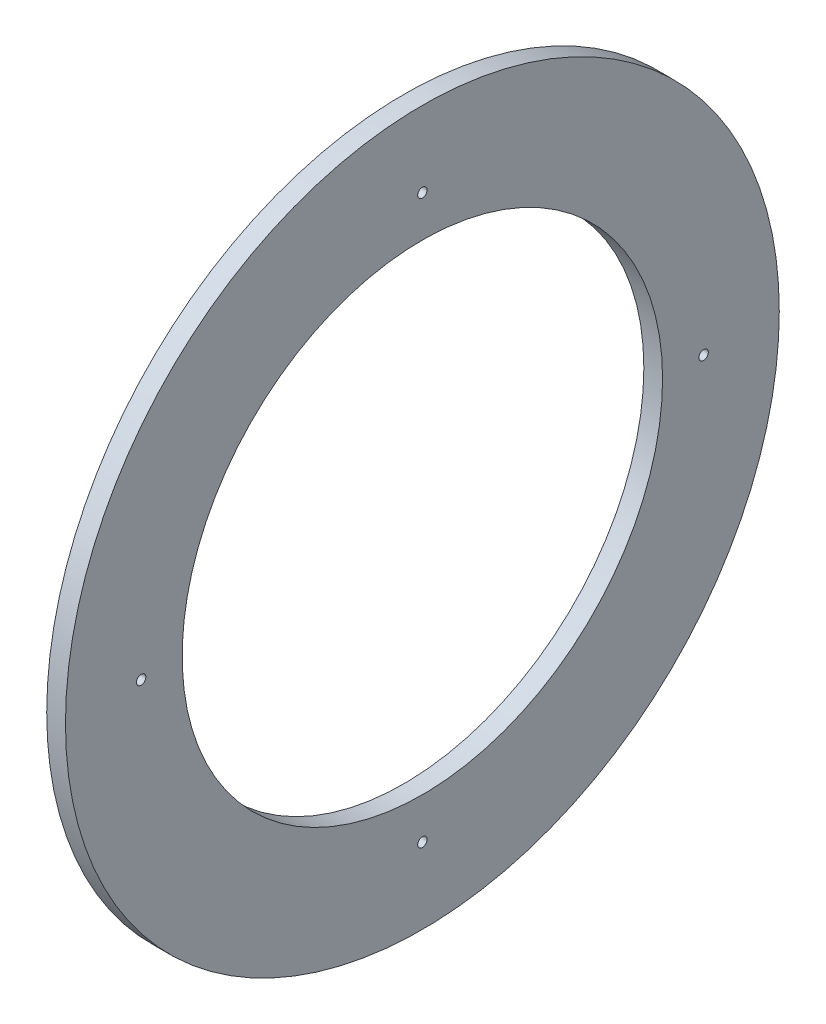
SolidWorks part; units mm, degrees
material "Teck"
ref_plane "Plan de face" through (0, 0, 0) normal (0, 0, 1) x (1, 0, 0)
ref_plane "Plan de dessus" through (0, 0, 0) normal (0, 1, 0) x (1, 0, 0)
ref_plane "Plan de droite" through (0, 0, 0) normal (1, 0, 0) x (0, 0, -1)
sketch "Esquisse1" plane through (0, 0, 0) normal (1, 0, 0) x (0, 0, -1)
  circle A0 centre (0, 0) radius 51.25
  circle A1 centre (0, 0) radius 76.15
  dimension "D1" = 102.5
  dimension "D2" = 152.3
extrude "Boss.-Extru.1" add sketch "Esquisse1" along normal blind 4
sketch "Sketch1" plane through (4, 0, 0) normal (1, 0, 0) x (0, 0, -1)
  circle A0 centre (0, 60) radius 1
  circle A1 centre (60, 0) radius 1
  circle A2 centre (0, -60) radius 1
  circle A3 centre (-60, 0) radius 1
  point P11 (0, 0)
  dimension "D2" = 2
  dimension "D3" = 60
  dimension "D1" = 4
extrude "air vents" cut sketch "Sketch1" against normal through all
